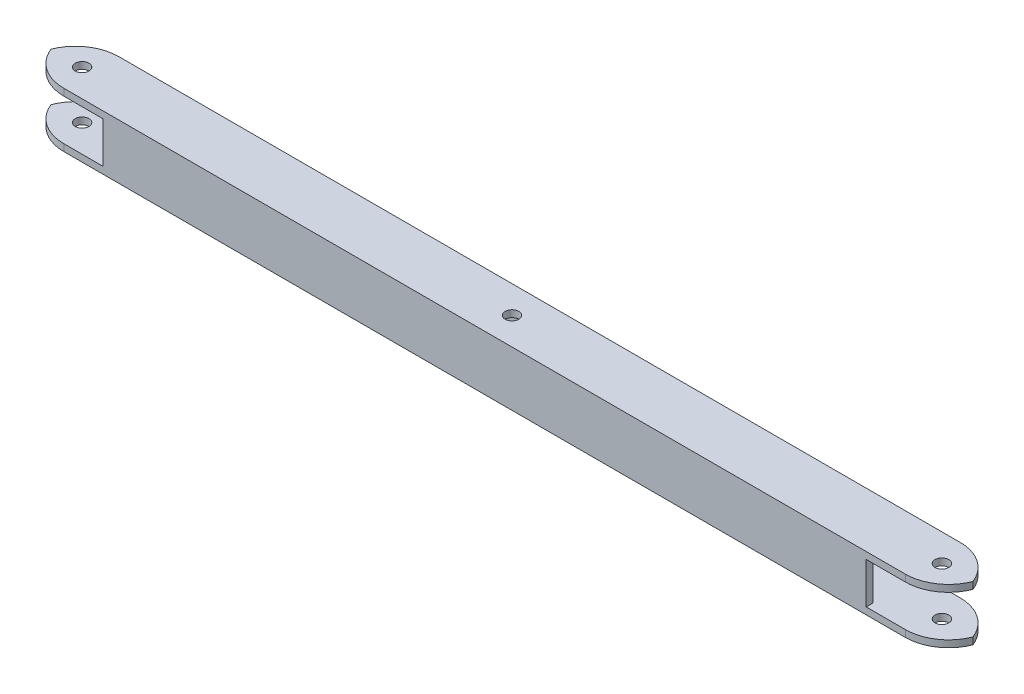
SolidWorks part; units mm, degrees
ref_plane "Front Plane" through (0, 0, 0) normal (0, 0, 1) x (1, 0, 0)
ref_plane "Top Plane" through (0, 0, 0) normal (0, 1, 0) x (1, 0, 0)
ref_plane "Right Plane" through (0, 0, 0) normal (1, 0, 0) x (0, 0, -1)
sketch "Sketch1" plane through (0, 0, 0) normal (0, 1, 0) x (1, 0, 0)
  line L0 (0, 0) -> (429.48, 0)
  line L1 (429.48, 0) -> (429.48, -25.4)
  line L2 (429.48, -25.4) -> (0, -25.4)
  line L3 (0, -25.4) -> (0, 0)
  line L4 (214.74, 0) -> (214.74, -25.4) construction
  line L5 (0, -12.7) -> (429.48, -12.7) construction
  circle A3 centre (214.74, -12.7) radius 3.175
  circle A6 centre (15.76, -12.7) radius 3.175
  circle A8 centre (413.72, -12.7) radius 3.175
  circle A9 centre (15.76, -12.7) radius 3.175 construction
  dimension "D3" = 6.35
  dimension "D5" = 198.98
  dimension "D4" = 6.35
  dimension "D1" = 429.48
  dimension "D2" = 25.4
extrude "Boss-Extrude1" add sketch "Sketch1" along normal blind 25.4
sketch "Sketch2" plane through (0, 0, 0) normal (-1, 0, 0) x (0, 0, 1)
  line L14 (3.175, 22.225) -> (3.175, 3.175)
  line L15 (3.175, 3.175) -> (22.225, 3.175)
  line L16 (22.225, 3.175) -> (22.225, 22.225)
  line L17 (22.225, 22.225) -> (3.175, 22.225)
  line L18 (3.175, 22.225) -> (3.175, 3.175)
  line L19 (3.175, 3.175) -> (22.225, 3.175)
  line L20 (22.225, 3.175) -> (22.225, 22.225)
  line L21 (22.225, 22.225) -> (3.175, 22.225)
  dimension "D1" = 3.175
extrude "Cut-Extrude1" cut sketch "Sketch2" against normal up to surface (429.48 mm away) up to face at (429.48, 12.7, 12.7)
sketch "Sketch4" plane through (0, 0, 0) normal (-1, 0, 0) x (0, 0, 1)
  line L1 (25.4, 25.4) -> (25.4, 0) construction
  line L2 (25.4, 22.225) -> (25.4, 3.175)
  line L3 (25.4, 3.175) -> (0, 3.175)
  line L4 (0, 25.4) -> (0, 0) construction
  line L5 (0, 3.175) -> (0, 22.225)
  line L7 (0, 22.225) -> (25.4, 22.225)
  line L8 (0, 25.4) -> (25.4, 25.4) construction
  line L9 (3.175, 3.175) -> (22.225, 3.175) construction
  dimension "D2" = 3.175
extrude "Cut-Extrude2" cut sketch "Sketch4" against normal blind 38.1
ref_plane "Plane1" through (214.74, 0, 0) normal (-1, 0, 0) x (0, 0, 1)
mirror "Mirror1" about plane through (214.74, 0, 0) normal (-1, 0, 0) of "Cut-Extrude2"
fillet "Fillet1" radius 20 8 edges at (429.48, 1.5875, 0) (429.48, 23.8125, 0) (429.48, 1.5875, 25.4) (429.48, 23.8125, 25.4) (0, 1.5875, 25.4) (0, 23.8125, 25.4) (0, 1.5875, 0) (0, 23.8125, 0)
sketch "Sketch5" plane through (0, 25.4, 0) normal (0, 1, 0) x (1, 0, 0)
  circle A0 centre (15.76, -12.7) radius 3.175 construction
  circle A1 centre (413.72, -12.7) radius 3.175 construction
